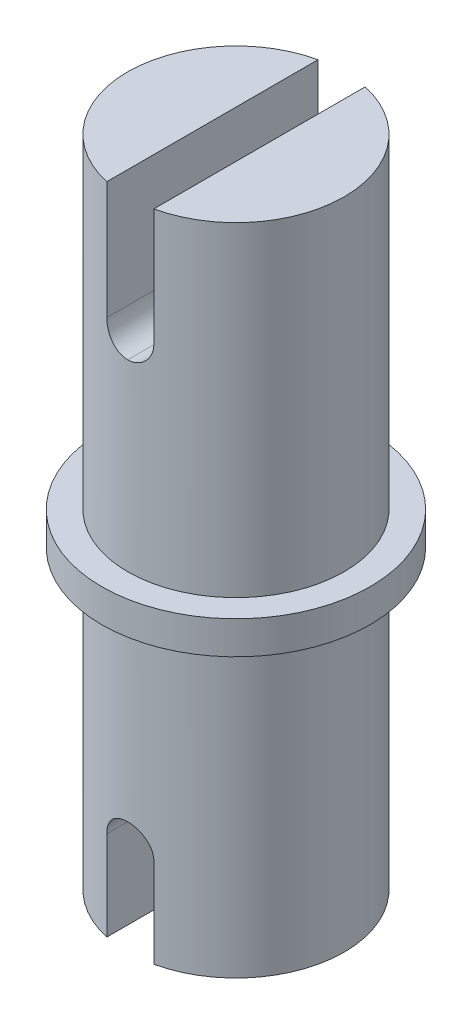
SolidWorks part; units mm, degrees
material "ABS"
ref_plane "Front Plane" through (0, 0, 0) normal (0, 0, 1) x (1, 0, 0)
ref_plane "Top Plane" through (0, 0, 0) normal (0, 1, 0) x (1, 0, 0)
ref_plane "Right Plane" through (0, 0, 0) normal (1, 0, 0) x (0, 0, -1)
sketch "Sketch2" plane through (0, 0, 0) normal (0, 1, 0) x (1, 0, 0)
  circle A0 centre (0, 0) radius 2.85
  dimension "D1" = 5.7
extrude "Boss-Extrude1" add sketch "Sketch2" along normal blind 0.35
sketch "Sketch4" plane through (0, 0.35, 0) normal (0, 1, 0) x (1, 0, 0)
  circle A0 centre (0, 0) radius 2.3
  dimension "D1" = 4.6
extrude "Boss-Extrude2" add sketch "Sketch4" along normal blind 6.9
sketch "Sketch5" plane through (0, 7.25, 0) normal (0, 1, 0) x (1, 0, 0)
  line L0 (-0.5, 2.245) -> (-0.5, -2.245)
  line L1 (0.5, 2.245) -> (0.5, -2.245)
  circle A0 centre (0, 0) radius 2.3 construction
  arc A1 (-0.5, 2.245) -> (0.5, 2.245) centre (0, 0) cw
  arc A2 (-0.5, -2.245) -> (0.5, -2.245) centre (0, 0) ccw
  dimension "D1" = 1
extrude "Cut-Extrude1" cut sketch "Sketch5" against normal blind 3
fillet "Fillet1" radius 0.5 2 edges at (0.5, 4.25, 0) (-0.5, 4.25, 0)
mirror "Mirror1" about plane through (0, 0, 0) normal (0, 1, 0) of "Boss-Extrude2", "Boss-Extrude1", "Cut-Extrude1", "Fillet1"
ref_plane "Plane1" through (0, -7.25, 0) normal (0, -1, 0) x (-1, 0, 0)
sketch "Sketch6" plane through (0, -7.25, 0) normal (0, -1, 0) x (-1, 0, 0)
  line L1 (0.5, 2.245) -> (0.5, -2.245)
  line L3 (-0.5, -2.245) -> (-0.5, 2.245)
  arc A2 (0.5, -2.245) -> (0.5, 2.245) centre (0, 0) ccw
  arc A3 (0.5, -2.245) -> (-0.5, 2.245) centre (0, 0) ccw
  arc A4 (-0.5, 2.245) -> (-0.5, -2.245) centre (0, 0) ccw
  arc A5 (-0.5, 2.245) -> (0.5, -2.245) centre (0, 0) ccw
  point P0 (0.4069, -2.245)
  dimension "D1" = 0
  dimension "D2" = 0
extrude "Cut-Extrude2" cut sketch "Sketch6" against normal blind 0.6
